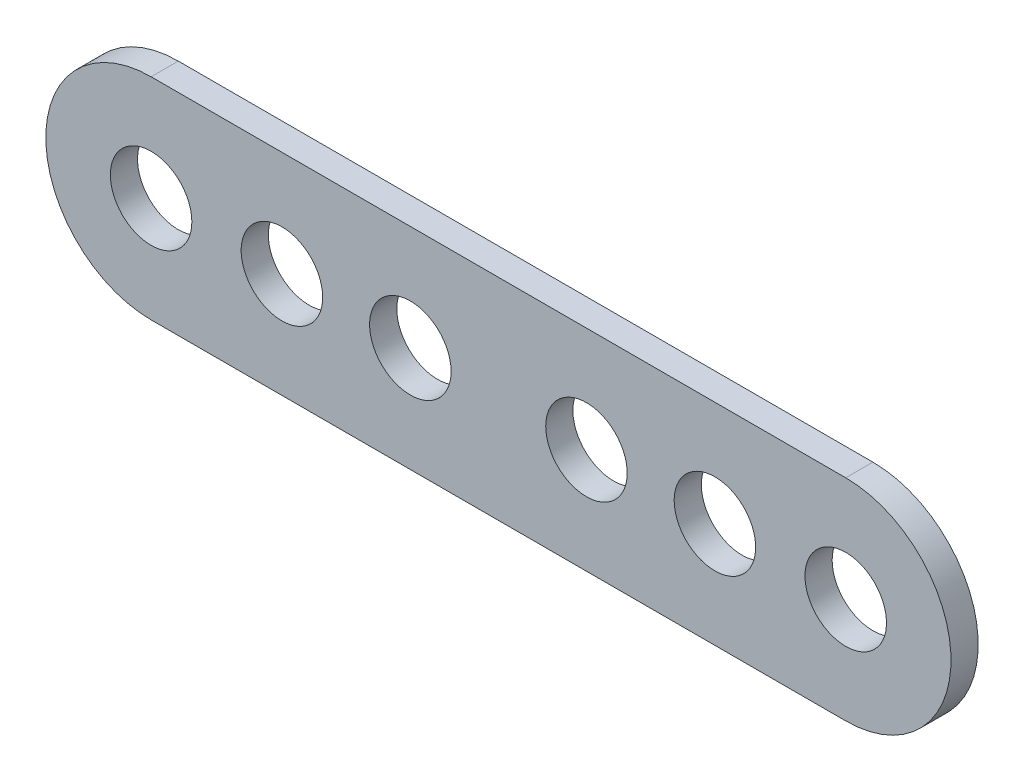
SolidWorks part; units mm, degrees
ref_plane "Спереди" through (0, 0, 0) normal (0, 0, 1) x (1, 0, 0)
ref_plane "Сверху" through (0, 0, 0) normal (0, 1, 0) x (1, 0, 0)
ref_plane "Справа" through (0, 0, 0) normal (1, 0, 0) x (0, 0, -1)
sketch "Эскиз1" plane through (0, 0, 0) normal (0, 0, 1) x (1, 0, 0)
  line L0 (25.5681, 7.75) -> (-25.5681, 7.75)
  line L1 (25.5681, -7.75) -> (-25.5681, -7.75)
  line L2 (0, 21.0997) -> (0, -20.7495) construction
  arc A0 (-25.5681, 7.75) -> (-25.5681, -7.75) centre (-25.5681, 0) ccw
  circle A1 centre (-25.5681, 0) radius 3
  circle A2 centre (-15.9376, 0) radius 3
  circle A3 centre (-6.4821, 0) radius 3
  circle A4 centre (6.4821, 0) radius 3
  circle A5 centre (15.9376, 0) radius 3
  circle A6 centre (25.5681, 0) radius 3
  arc A7 (25.5681, 7.75) -> (25.5681, -7.75) centre (25.5681, 0) cw
  point P0 (-6.4821, 0)
  point P2 (0, 7.75)
  point P21 (0, -7.75)
extrude "Бобышка-Вытянуть1" add sketch "Эскиз1" along normal blind 2
